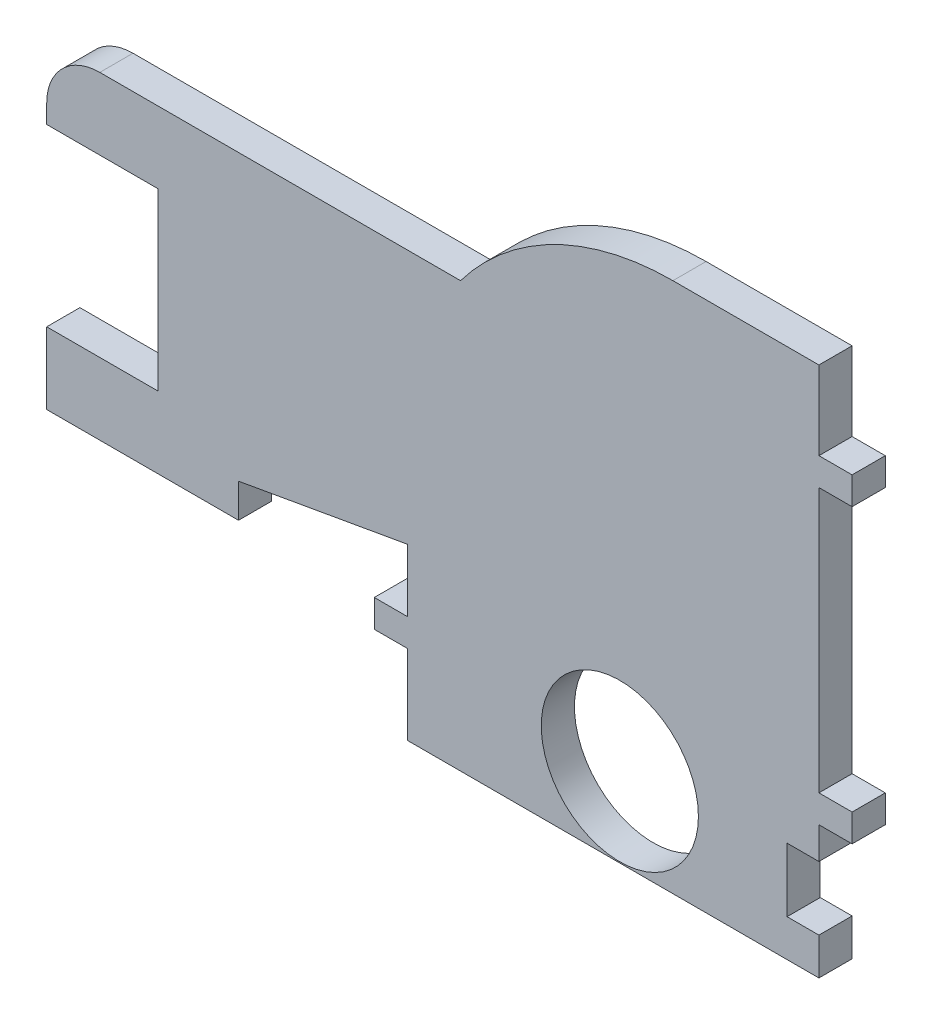
SolidWorks part; units mm, degrees
material "Balsa"
ref_plane "Front Plane" through (0, 0, 0) normal (0, 0, 1) x (1, 0, 0)
ref_plane "Top Plane" through (0, 0, 0) normal (0, 1, 0) x (1, 0, 0)
ref_plane "Right Plane" through (0, 0, 0) normal (1, 0, 0) x (0, 0, -1)
sketch "Sketch1" plane through (0, 0, 0) normal (0, 0, 1) x (1, 0, 0)
  line L0 (0, -1000.1535) -> (0, 48999.8465) construction
  line L1 (-7.62, 16.51) -> (-24.8789, 16.51)
  line L2 (-1000, 0) -> (49000, 0) construction
  line L3 (9.525, 16.51) -> (11.1125, 16.51)
  line L4 (2.54, 21.59) -> (9.525, 21.59)
  line L5 (-10.16, 8.89) -> (-10.16, -3.81)
  line L6 (-10.16, -3.81) -> (9.525, -3.81)
  line L7 (9.525, 21.59) -> (9.525, -3.81)
  line L8 (-11.7475, 0) -> (-10.16, 0)
  line L9 (-11.7475, 0) -> (-11.7475, 1.3208)
  line L10 (-11.7475, 1.3208) -> (-10.16, 1.3208)
  line L11 (-10.16, 0) -> (-10.16, 1.3208)
  line L12 (9.525, 2.54) -> (11.1125, 2.54)
  line L13 (9.525, 2.54) -> (9.525, 3.8608)
  line L14 (9.525, 3.8608) -> (11.1125, 3.8608)
  line L15 (11.1125, 2.54) -> (11.1125, 3.8608)
  line L16 (9.525, 16.51) -> (9.525, 17.8308)
  line L17 (9.525, 17.8308) -> (11.1125, 17.8308)
  line L18 (11.1125, 16.51) -> (11.1125, 17.8308)
  line L19 (-27.4189, 13.97) -> (-27.4189, 1.27)
  line L20 (-27.4189, 1.27) -> (-10.16, 4.318)
  line L21 (-27.4189, 13.081) -> (-22.0849, 13.081)
  line L22 (-22.0849, 13.081) -> (-22.0849, 4.699)
  line L23 (-22.0849, 4.699) -> (-27.4189, 4.699)
  line L24 (-27.4189, 1.27) -> (-18.2418, 1.27)
  line L25 (-18.2418, 1.27) -> (-18.2418, 2.8907)
  line L27 (9.525, 1.016) -> (8.001, 1.016)
  line L28 (9.525, 1.016) -> (9.525, -2.032)
  line L29 (9.525, -2.032) -> (8.001, -2.032)
  line L30 (8.001, 1.016) -> (8.001, -2.032)
  circle A0 centre (0, 0) radius 3.7592
  arc A1 (-24.8789, 16.51) -> (-27.4189, 13.97) centre (-24.8789, 13.97) ccw
  arc A3 (2.54, 21.59) -> (-10.16, 8.89) centre (2.54, 8.89) ccw
  dimension "D1" = 7.5184
  dimension "D4" = 3.81
  dimension "D3" = 3.7592
  dimension "D5" = 1.5875
  dimension "D9" = 12.7
  dimension "D10" = 1.5875
  dimension "D18" = 2.54
  dimension "D2" = 25.4
  dimension "D6" = 9.525
  dimension "D7" = 1.3208
  dimension "D8" = 19.685
  dimension "D11" = 2.54
  dimension "D12" = 1.3208
  dimension "D13" = 1.3208
  dimension "D14" = 1.5875
  dimension "D15" = 1.524
  dimension "D16" = 1.016
  dimension "D17" = 3.048
extrude "Boss-Extrude1" add sketch "Sketch1" along normal blind 1.5875 contours L4 A3 L5 L6 L7 A0 | L10 L9 L8 L5 | L3 L18 L17 L7 | L12 L15 L14 L7 | A3 L1 L19 L20 L5 | L24 L25 L20 region at (-17.4687, 9.9034, 0) region at (0.1298, 9.1228, 0) region at (10.3187, 17.1704, 0) region at (-10.9538, 0.6604, 0) region at (-21.3008, 1.8102, 0) region at (10.3187, 3.2004, 0)
move or copy body "Body-Move/Copy1" [suppressed] bodies to move or copy 101
